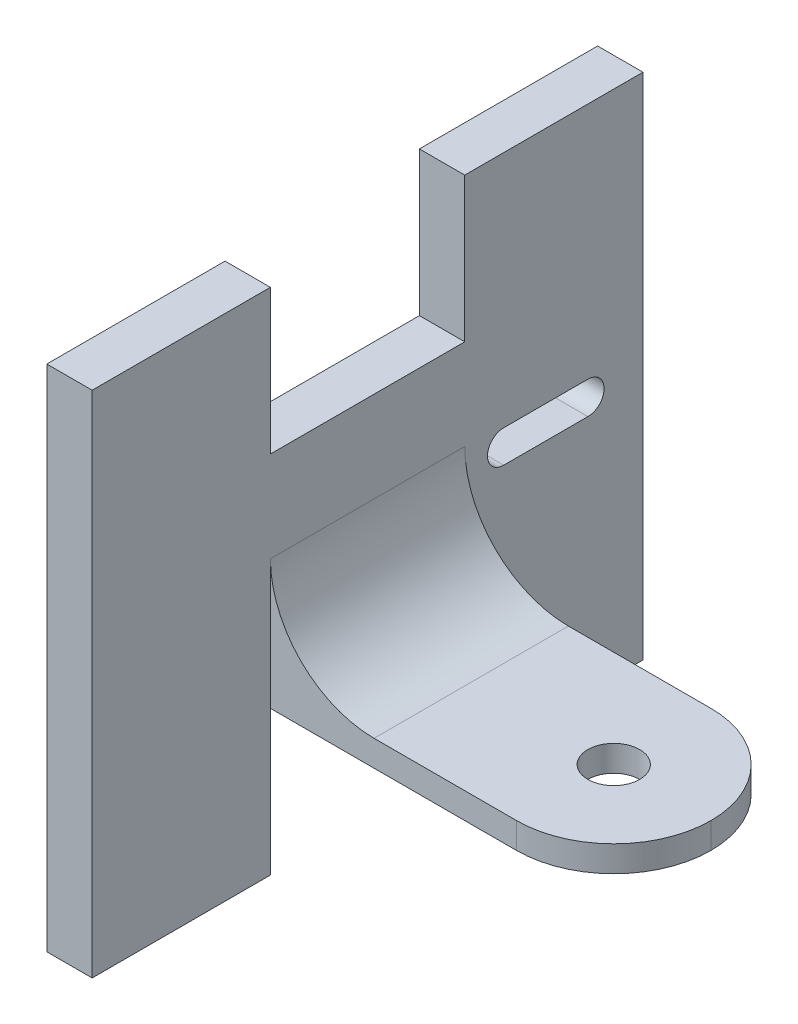
SolidWorks part; units mm, degrees
ref_plane "Front" through (0, 0, 0) normal (0, 0, 1) x (1, 0, 0)
ref_plane "Top" through (0, 0, 0) normal (0, 1, 0) x (1, 0, 0)
ref_plane "Right" through (0, 0, 0) normal (1, 0, 0) x (0, 0, -1)
sketch "草圖1" plane through (0, 0, 0) normal (0, 1, 0) x (1, 0, 0)
  line L0 (-35.2735, 0) -> (35.2735, 0) construction
  line L1 (-30, -15) -> (30, -15)
  line L2 (-30, -15) -> (-30, 15)
  line L3 (-30, 15) -> (30, 15)
  line L4 (30, -15) -> (30, 15)
  line L5 (-30, -15) -> (30, 15) construction
  line L6 (-30, 15) -> (30, -15) construction
  circle A0 centre (15, 0) radius 4
  point P21 (0, 0)
  point P25 (0, 0)
  dimension "D1" = 8
  dimension "D2" = 30
  dimension "D3" = 60
  dimension "D4" = 15
extrude "填料-伸長1" add sketch "草圖1" along normal blind 4
sketch "草圖2" plane through (0, 4, 0) normal (0, 1, 0) x (1, 0, 0)
  line L0 (-30, -15) -> (30, -15) construction
  line L1 (-30, 15) -> (-23, 15)
  line L2 (-30, 15) -> (-30, -15)
  line L3 (-30, -15) -> (-23, -15)
  line L4 (-23, 15) -> (-23, -15)
  dimension "D1" = 7
extrude "填料-伸長2" add sketch "草圖2" along normal blind 30
sketch "草圖3" plane through (-30, 0, 0) normal (-1, 0, 0) x (0, 0, 1)
  line L0 (0, 11.9988) -> (0, -11.9988) construction
  circle A0 centre (0, 20) radius 11
  point P6 (0, 0)
  dimension "D1" = 22
  dimension "D2" = 20
extrude "除料-伸長1" [suppressed] cut sketch "草圖3" against normal through all
sketch "草圖4" plane through (0, 0, -15) normal (0, 0, -1) x (-1, 0, 0)
  line L0 (26.5, 75.0073) -> (26.5, -7.0073) construction
  line L2 (23, 34) -> (30, 34) construction
  line L3 (55.9217, 17) -> (4.0783, 17) construction
  line L5 (30, 34) -> (30, 0) construction
  line L7 (23, -22.2864) -> (30, -22.2864)
  line L8 (23, -22.2864) -> (23, 56.2864)
  line L9 (23, 56.2864) -> (30, 56.2864)
  line L10 (30, -22.2864) -> (30, 56.2864)
  line L11 (26.5, 56.2864) -> (26.5, -22.2864) construction
  line L12 (23, 17) -> (30, 17) construction
  point P5 (26.5, 34)
  point P7 (26.5, 17)
  point P10 (26.5, 17)
  point P11 (30, 17)
  point P15 (30, -14.2735)
  point P16 (30, 17)
  point P17 (30, -22.2864)
extrude "填料-伸長3" add sketch "草圖4" along normal blind 27.51
mirror "鏡射1" about plane through (0, 0, 0) normal (0, 0, 1) of "填料-伸長3"
fillet "圓角1" radius 16 1 edges at (-23, 4, 0)
sketch "草圖5" plane through (-23, 0, 0) normal (1, 0, 0) x (0, 0, -1)
  line L0 (8.9713, 17) -> (76.0487, 17) construction
  line L2 (42.51, 56.2864) -> (42.51, -22.2864) construction
  line L3 (21.01, 17) -> (34.01, 17) construction
  line L4 (21.01, 19.5) -> (34.01, 19.5)
  line L5 (21.01, 14.5) -> (34.01, 14.5)
  arc A0 (21.01, 19.5) -> (21.01, 14.5) centre (21.01, 17) ccw
  arc A1 (34.01, 14.5) -> (34.01, 19.5) centre (34.01, 17) ccw
  point P5 (42.51, 17)
  point P7 (27.51, 17)
  point P12 (37.2985, 17)
  point P13 (33.801, 17)
  dimension "D1" = 2.5
  dimension "D2" = 15
  dimension "D3" = 13
extrude "除料-伸長2" cut sketch "草圖5" against normal through all
fillet "圓角2" radius 15 2 edges at (30, 2, 15) (30, 2, -15)
